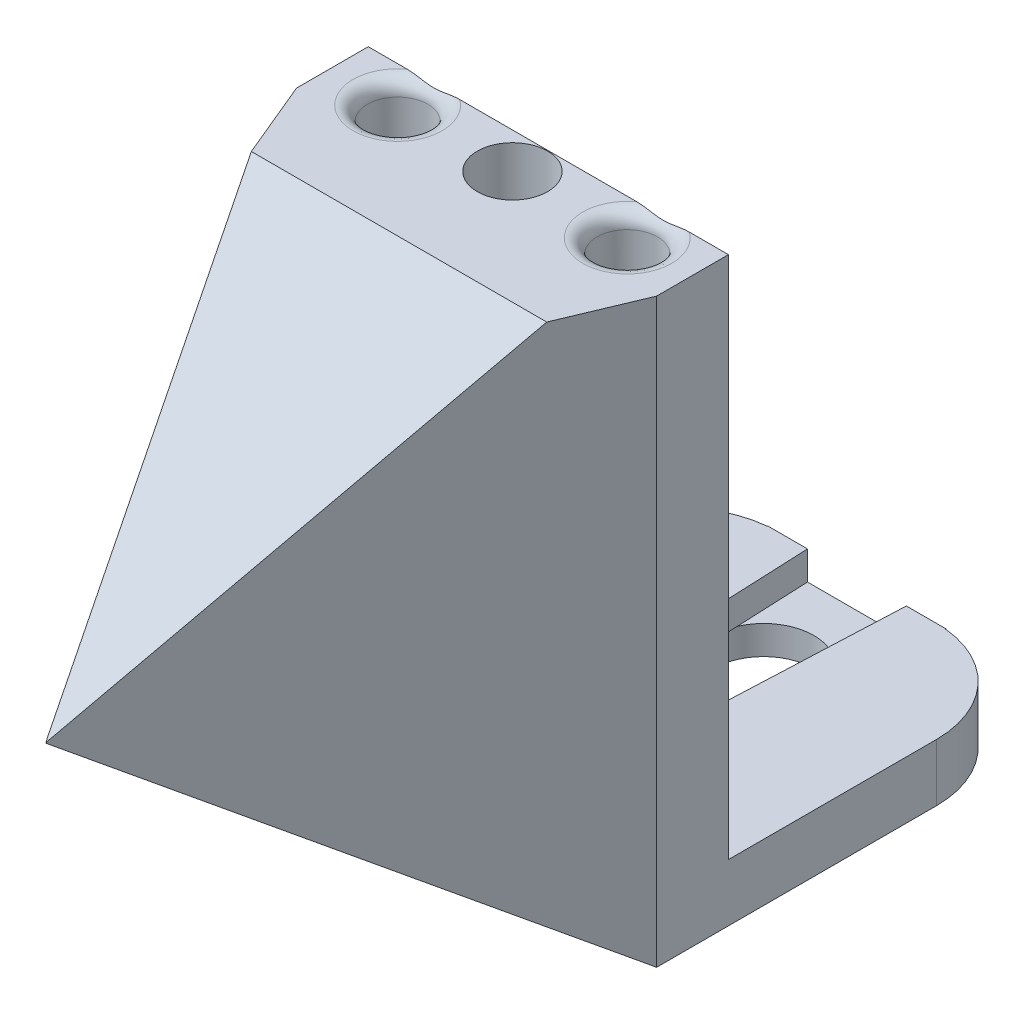
SolidWorks part; units mm, degrees
ref_plane "Front Plane" through (0, 0, 0) normal (0, 0, 1) x (1, 0, 0)
ref_plane "Top Plane" through (0, 0, 0) normal (0, 1, 0) x (1, 0, 0)
ref_plane "Right Plane" through (0, 0, 0) normal (1, 0, 0) x (0, 0, -1)
sketch "Sketch4" plane through (0, 0, 0) normal (0, 0, 1) x (1, 0, 0)
  line L1 (-6.23, -9.975) -> (6.23, -9.975)
  line L2 (-6.23, -9.975) -> (-6.23, 7.275)
  line L3 (-6.23, 7.275) -> (6.23, 7.275)
  line L4 (6.23, -9.975) -> (6.23, 7.275)
  point P4 (0, 7.275)
  dimension "D1" = 12.46
  dimension "D2" = 17.25
  dimension "D3" = 9.975
extrude "Boss-Extrude3" add sketch "Sketch4" along normal blind 6
sketch "Sketch8" plane through (0, -9.975, 0) normal (0, -1, 0) x (-1, 0, 0)
  circle A0 centre (0, -23.55) radius 12.5468
  circle A1 centre (0, -23.55) radius 11.15
  dimension "D1" = 22.3
  dimension "D2" = 23.55
extrude "Boss-Extrude6" add sketch "Sketch8" along normal blind 7.3 and the other way up to surface (17.25 mm away) other way up to face at (0, 7.275, 3)
sketch "Sketch5" plane through (0, 7.275, 0) normal (0, 1, 0) x (1, 0, 0)
  line L8 (12.5468, -23.55) -> (12.5468, 0)
  line L9 (12.5468, 0) -> (6.23, 0)
  line L10 (-12.5468, -23.55) -> (-12.5468, 0)
  line L11 (-12.5468, 0) -> (-6.23, 0)
  line L12 (-6.23, 0) -> (-6.23, -29.7)
  line L14 (6.23, -29.7) -> (6.23, 0)
  line L15 (-6.23, -29.7) -> (6.23, -29.7)
  line L16 (6.23, -6) -> (-6.23, -6) construction
  circle A0 centre (0, -23.55) radius 12.5468 construction
  arc A1 (-12.5468, -23.55) -> (12.5468, -23.55) centre (0, -23.55) ccw
  dimension "D1" = 23.7
  dimension "D2" = 23.55
extrude "Boss-Extrude4" add sketch "Sketch5" against normal up to surface (17.25 mm away) up to face at (0, -9.975, 3)
sketch "Sketch6" plane through (0, 7.275, 0) normal (0, 1, 0) x (1, 0, 0)
  line L0 (6.23, -6) -> (-6.23, -6) construction
  line L3 (6.23, -29.7) -> (-6.23, -29.7) construction
  circle A0 centre (0, -3.5) radius 2
  circle A1 centre (0, -32.2) radius 2
  dimension "D1" = 4
  dimension "D3" = 4
  dimension "D2" = 2.5
  dimension "D4" = 2.5
extrude "Cut-Extrude1" cut sketch "Sketch6" against normal blind 5
chamfer "Chamfer1" distance 0.5 angle 60 2 edges at (0, 7.275, 5.5) (0, 7.275, 34.2) first distance on face at (0, 7.275, 5.5)
sketch "Sketch10" plane through (0, 7.275, 0) normal (0, 1, 0) x (1, 0, 0)
  line L1 (-6.23, -6) -> (6.23, -6)
  line L2 (-6.23, -6) -> (-6.23, -29.7)
  line L3 (-6.23, -29.7) -> (6.23, -29.7)
  line L4 (6.23, -6) -> (6.23, -29.7)
extrude "Cut-Extrude3" cut sketch "Sketch10" against normal up to surface (17.25 mm away) up to face at (0, -9.975, 10.3399)
ref_plane "Plane1" through (0, 0, 36.0968) normal (0, 0, 1) x (1, 0, 0)
sketch "Sketch11" plane through (0, 0, 36.0968) normal (0, 0, 1) x (1, 0, 0)
  line L0 (-11.15, -9.975) -> (11.15, -9.975) construction
  line L1 (-2.5, -6.975) -> (2.5, -6.975)
  line L2 (-2.5, -6.975) -> (-2.5, -9.975)
  line L3 (-2.5, -9.975) -> (2.5, -9.975)
  line L4 (2.5, -6.975) -> (2.5, -9.975)
  point P4 (0, -6.975)
  dimension "D1" = 0
  dimension "D2" = 5
  dimension "D3" = 3
extrude "Cut-Extrude4" cut sketch "Sketch11" against normal up to next
sketch "Sketch13" plane through (0, -17.275, 0) normal (0, -1, 0) x (1, 0, 0)
  line L0 (-12.5468, 23.55) -> (-12.5468, 0)
  line L1 (-12.5468, 0) -> (12.5468, 0)
  line L2 (12.5468, 0) -> (12.5468, 23.55)
  arc A0 (-12.5468, 23.55) -> (12.5468, 23.55) centre (0, 23.55) ccw
  point P3 (0, 0)
extrude "Boss-Extrude7" add sketch "Sketch13" against normal up to surface (7.3 mm away) up to face at (0, -9.975, 10.3399)
sketch "Sketch15" plane through (0, 7.275, 0) normal (0, 1, 0) x (1, 0, 0)
  line L0 (-12.5468, 0) -> (12.5468, 0)
  line L1 (12.5468, 0) -> (12.5468, -23.55)
  line L2 (-12.5468, 0) -> (-12.5468, -23.55)
  line L3 (6.23, -6) -> (6.23, -29.7) construction
  line L4 (-6.23, -0.8) -> (6.23, -0.8)
  line L5 (-6.23, -0.8) -> (-6.23, -33.5)
  line L6 (-5.23, -34.5) -> (5.23, -34.5)
  line L7 (6.23, -0.8) -> (6.23, -33.5)
  arc A0 (-12.5468, -23.55) -> (12.5468, -23.55) centre (0, -23.55) ccw
  circle A1 centre (0, -3.5) radius 2 construction
  arc A2 (5.23, -34.5) -> (6.23, -33.5) centre (5.23, -33.5) ccw
  arc A3 (-6.23, -33.5) -> (-5.23, -34.5) centre (-5.23, -33.5) ccw
  point P15 (0, -0.8)
  dimension "D1" = 0.8
  dimension "D3" = 1
  dimension "D2" = 2.7
  dimension "D4" = 0
  dimension "D5" = 34.5
extrude "Boss-Extrude9" add sketch "Sketch15" along normal blind 10
sketch "Sketch17" plane through (-12.5468, 4.7282, 0) normal (1, 0, 0) x (0, -1, 0)
  line L0 (26.9782, 26.5) -> (26.9782, 0)
  line L1 (26.9782, 0) -> (-17.5218, 0)
  line L2 (-17.5218, 0) -> (-17.5218, 26.5)
  line L3 (-17.5218, 26.5) -> (-13.5218, 26.5)
  line L4 (-13.5218, 26.5) -> (-13.5218, 5)
  line L5 (-13.5218, 5) -> (22.9782, 5)
  line L6 (22.9782, 5) -> (22.9782, 26.5)
  line L7 (22.9782, 26.5) -> (26.9782, 26.5)
  point P2 (4.7282, 5)
  point P10 (4.7282, 0)
  dimension "D1" = 4
  dimension "D2" = 36.5
  dimension "D3" = 0
  dimension "D4" = 26.5
  dimension "D5" = 5
extrude "Boss-Extrude10" add sketch "Sketch17" along normal up to surface (25.0936 mm away) up to face at (12.5468, 0, 11.775)
sketch "Sketch18" plane through (0, -18.25, 0) normal (0, 1, 0) x (0, 0, 1)
  line L0 (-26.5, -12.5468) -> (-26.5, 12.5468) construction
  line L1 (-26.5, 6.2191) -> (-5, 6.2191)
  line L2 (-26.5, 6.2191) -> (-26.5, -6.2191)
  line L3 (-26.5, -6.2191) -> (-5, -6.2191)
  line L4 (-5, 6.2191) -> (-5, -6.2191)
  line L5 (-5, -12.5468) -> (-5, 12.5468) construction
  point P6 (-26.5, 0)
  point P7 (-26.5, 0)
  dimension "D1" = 0
extrude "Cut-Extrude5" cut sketch "Sketch18" against normal blind 2
sketch "Sketch19" plane through (0, -20.25, 0) normal (0, 1, 0) x (0, 0, 1)
  line L0 (-26.5, -12.5468) -> (-26.5, 12.5468) construction
  line L1 (-26.5, 12.5468) -> (-26.5, -12.5468) construction
  circle A0 centre (-20, 0) radius 3.5
  point P7 (-26.5, 0)
  dimension "D1" = 7
  dimension "D2" = 6.5
extrude "Cut-Extrude6" cut sketch "Sketch19" against normal through all both and the other way through all
fillet "Fillet1" radius 7 4 edges at (12.5468, -20.25, -26.5) (-12.5468, -20.25, -26.5) (-12.5468, 20.25, -26.5) (12.5468, 20.25, -26.5)
ref_plane "Plane2" through (0, 0, 0) normal (1, 0, 0) x (0, 0, -1)
ref_plane "Plane3" through (0, 0, 0) normal (0, -1, 0) x (-1, 0, 0)
sketch "Sketch20" plane through (0, 17.275, 0) normal (0, 1, 0) x (1, 0, 0)
  line L1 (12.5468, 0) -> (-12.5468, 0)
  line L2 (12.5468, 0) -> (12.5468, -36.0968)
  line L3 (12.5468, -36.0968) -> (-12.5468, -36.0968)
  line L4 (-12.5468, 0) -> (-12.5468, -36.0968)
extrude "Cut-Extrude7" cut sketch "Sketch20" against normal through all both and the other way through all
sketch "Sketch21" plane through (0, 22.25, 0) normal (0, 1, 0) x (1, 0, 0)
  line L0 (12.5468, 0) -> (-0.0254, -30)
  line L1 (-0.0254, -30) -> (-12.5468, 0)
  line L2 (-12.5468, 0) -> (12.5468, 0)
  dimension "D1" = 30
extrude "Boss-Extrude11" add sketch "Sketch21" against normal up to vertex (44.5 mm away) up to point (-12.5468, -22.25, 0)
sketch "Sketch22" plane through (0, 0, 0) normal (1, 0, 0) x (0, 0, -1)
  line L13 (0, 22.25) -> (-30, 0.01)
  line L14 (-30, -22.25) -> (-30, 22.25) construction
  line L15 (-30, 0.01) -> (-30, 22.25)
  line L16 (-30, 22.25) -> (0, 22.25)
  line L17 (0, -22.25) -> (-30, -22.25)
  line L18 (-30, -22.25) -> (-30, -0.01)
  line L19 (-30, -0.01) -> (0, -22.25)
  dimension "D1" = 0.02
  dimension "D2" = 0.01
extrude "Cut-Extrude8" cut sketch "Sketch22" against normal through all both and the other way through all
sketch "Sketch23" plane through (0, 0, 0) normal (0, 0, -1) x (-1, 0, 0)
  line L0 (12.5468, 18.25) -> (0, 0)
  line L1 (0, 0) -> (12.5468, -22.25)
  line L2 (12.5468, -22.25) -> (12.5468, 18.25)
extrude "Cut-Extrude9" cut sketch "Sketch23" against normal through all
sketch "Sketch24" plane through (0, 22.25, 0) normal (0, 1, 0) x (1, 0, 0)
  circle A0 centre (0, 20) radius 6.5
  dimension "D1" = 13
extrude "Boss-Extrude12" add sketch "Sketch24" against normal blind 5
sketch "Sketch25" plane through (0, 17.25, 0) normal (0, -1, 0) x (1, 0, 0)
  circle A0 centre (0, -20) radius 6.075
  dimension "D1" = 12.15
extrude "Boss-Extrude13" add sketch "Sketch25" along normal blind 5
fillet "Fillet2" radius 1 1 edges at (0, 12.25, -26.075)
sketch "Sketch26" plane through (0, -20.25, 0) normal (0, 1, 0) x (1, 0, 0)
  line L0 (-6.2191, 5) -> (-2.5, 5)
  line L1 (12.5468, 5) -> (-12.5468, 5) construction
  line L2 (-2.5, 5) -> (-3.1585, 20)
  line L4 (3.1585, 20) -> (3.4438, 26.5)
  line L5 (-6.2191, 26.5) -> (-6.2191, 5)
  line L6 (2.5, 5) -> (6.2191, 5)
  line L7 (6.2191, 5) -> (6.2191, 26.5)
  line L8 (3.4438, 26.5) -> (6.2191, 26.5)
  line L10 (3.1585, 20) -> (2.5, 5)
  line L11 (0, -10.725) -> (0, 10.725) construction
  line L13 (-3.1585, 20) -> (-3.4439, 26.5)
  line L14 (-3.4439, 26.5) -> (-6.2191, 26.5)
  line L15 (6.2191, 5) -> (6.2191, 26.4676) construction
  line L16 (5.5468, 26.5) -> (-5.5468, 26.5) construction
  circle A0 centre (0, 20) radius 3.5 construction
  dimension "D1" = 5
  dimension "D2" = 2.5
  dimension "D3" = 0
  dimension "D4" = 0
  dimension "D5" = 6.317
  dimension "D6" = 3.1585
extrude "Boss-Extrude14" add sketch "Sketch26" along normal up to surface (2 mm away) up to face at (-9.7194, -18.25, -14.2975)
sketch "Sketch27" plane through (0, -22.25, 0) normal (0, -1, 0) x (1, 0, 0)
  line L0 (0, -10.725) -> (0, 10.725) construction
  circle A0 centre (0, -10) radius 0.75
  circle A1 centre (0, -20) radius 3.5 construction
  circle A2 centre (0, -7.5) radius 0.75
  circle A3 centre (0, -12.5) radius 0.75
  dimension "D1" = 1.5
  dimension "D4" = 7.5
  dimension "D5" = 12.5
  dimension "D2" = 10
  dimension "D3" = 0
extrude "Cut-Extrude10" cut sketch "Sketch27" against normal up to next
sketch "Sketch28" plane through (12.5468, 0, 0) normal (1, 0, 0) x (0, 0, -1)
  line L1 (5, 18.25) -> (-20.6857, 18.25)
  line L3 (-20.6857, 18.25) -> (-20.6857, 31.0837)
  line L11 (-20.6857, 31.0837) -> (38.2934, 31.0837)
  line L12 (38.2934, 31.0837) -> (38.2934, 6.4281)
  line L13 (38.2934, 6.4281) -> (5, 6.4281)
  line L14 (5, -18.25) -> (5, 18.25) construction
  line L15 (5, 6.4281) -> (5, 18.25)
extrude "Cut-Extrude11" cut sketch "Sketch28" against normal through all
sketch "Sketch29" plane through (0, 18.25, 0) normal (0, 1, 0) x (1, 0, 0)
  line L0 (0, -10.725) -> (0, 10.725) construction
  line L1 (12.5468, 5) -> (-12.5468, 5) construction
  circle A0 centre (-8, 2.5) radius 2.1
  circle A1 centre (0, 2.5) radius 2.45
  circle A2 centre (8, 2.5) radius 2.1
  point P6 (0, 0)
  dimension "D1" = 4.2
  dimension "D2" = 4.9
  dimension "D3" = 16
  dimension "D4" = 8
  dimension "D5" = 0
  dimension "D6" = 2.5
extrude "Cut-Extrude12" cut sketch "Sketch29" against normal blind 7
fillet "Fillet3" radius 10 2 edges at (-6.2734, 9.125, 0) (-6.2734, -11.125, 0)
fillet "Fillet4" radius 1 2 edges at (8, 18.25, -0.4) (-8, 18.25, -0.4)
